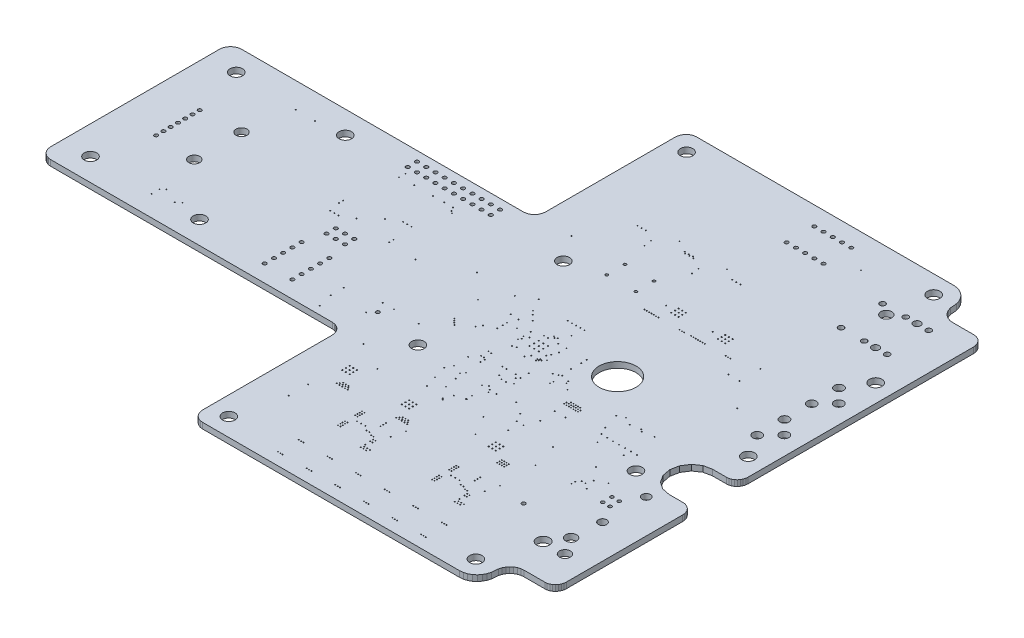
SolidWorks part; units mm, degrees
ref_plane "Front Plane" through (0, 0, 0) normal (0, 0, 1) x (1, 0, 0)
ref_plane "Top Plane" through (0, 0, 0) normal (0, 1, 0) x (1, 0, 0)
ref_plane "Right Plane" through (0, 0, 0) normal (1, 0, 0) x (0, 0, -1)
ref_plane "Dielectric_Layer Layer 1" through (0, 1.6, 0) normal (0, 1, 0) x (1, 0, 0)
sketch "Sketch1" plane through (0, 0, 0) normal (0, 1, 0) x (1, 0, 0)
  line L0 (90.797, -59) -> (91.3624, -58.9424)
  line L1 (91.3624, -58.9424) -> (91.906, -58.7716)
  line L2 (91.906, -58.7716) -> (92.4069, -58.4944)
  line L3 (92.4069, -58.4944) -> (92.8461, -58.1213)
  line L4 (92.8461, -58.1213) -> (93.2064, -57.6667)
  line L5 (93.2064, -57.6667) -> (93.4742, -57.148)
  line L6 (93.4742, -57.148) -> (93.6391, -56.5853)
  line L7 (93.6391, -56.5853) -> (93.6948, -56)
  line L8 (93.6948, -56) -> (93.6948, -24)
  line L9 (93.6948, -24) -> (93.6391, -23.4147)
  line L10 (93.6391, -23.4147) -> (93.4742, -22.8519)
  line L11 (93.4742, -22.8519) -> (93.2064, -22.3333)
  line L12 (93.2064, -22.3333) -> (92.8461, -21.8787)
  line L13 (92.8461, -21.8787) -> (92.4069, -21.5056)
  line L14 (92.4069, -21.5056) -> (91.906, -21.2284)
  line L15 (91.906, -21.2284) -> (91.3624, -21.0576)
  line L16 (91.3624, -21.0576) -> (90.797, -21)
  line L17 (90.797, -21) -> (86.9333, -21)
  line L18 (86.9333, -21) -> (84.7155, -20.5433)
  line L19 (84.7155, -20.5433) -> (82.8353, -19.2426)
  line L20 (82.8353, -19.2426) -> (81.5789, -17.2961)
  line L21 (81.5789, -17.2961) -> (81.1378, -15)
  line L22 (81.1378, -15) -> (81.5789, -12.7039)
  line L23 (81.5789, -12.7039) -> (82.8353, -10.7574)
  line L24 (82.8353, -10.7574) -> (84.7155, -9.4567)
  line L25 (84.7155, -9.4567) -> (86.9333, -9)
  line L26 (86.9333, -9) -> (90.797, -9)
  line L27 (90.797, -9) -> (91.3624, -8.9424)
  line L28 (91.3624, -8.9424) -> (91.906, -8.7716)
  line L29 (91.906, -8.7716) -> (92.4069, -8.4944)
  line L30 (92.4069, -8.4944) -> (92.8461, -8.1213)
  line L31 (92.8461, -8.1213) -> (93.2064, -7.6667)
  line L32 (93.2064, -7.6667) -> (93.4742, -7.148)
  line L33 (93.4742, -7.148) -> (93.6391, -6.5853)
  line L34 (93.6391, -6.5853) -> (93.6948, -6)
  line L35 (93.6948, -6) -> (93.6948, 56)
  line L36 (93.6948, 56) -> (93.6391, 56.5853)
  line L37 (93.6391, 56.5853) -> (93.4742, 57.148)
  line L38 (93.4742, 57.148) -> (93.2064, 57.6667)
  line L39 (93.2064, 57.6667) -> (92.8461, 58.1213)
  line L40 (92.8461, 58.1213) -> (92.4069, 58.4944)
  line L41 (92.4069, 58.4944) -> (91.906, 58.7716)
  line L42 (91.906, 58.7716) -> (91.3624, 58.9424)
  line L43 (91.3624, 58.9424) -> (90.797, 59)
  line L44 (90.797, 59) -> (85.0015, 59)
  line L45 (85.0015, 59) -> (84.2477, 59.0769)
  line L46 (84.2477, 59.0769) -> (83.5229, 59.3045)
  line L47 (83.5229, 59.3045) -> (82.8549, 59.6741)
  line L48 (82.8549, 59.6741) -> (82.2694, 60.1716)
  line L49 (82.2694, 60.1716) -> (81.7889, 60.7777)
  line L50 (81.7889, 60.7777) -> (81.4319, 61.4693)
  line L51 (81.4319, 61.4693) -> (81.212, 62.2196)
  line L52 (81.212, 62.2196) -> (81.1378, 63)
  line L53 (81.1378, 63) -> (81.045, 63.9755)
  line L54 (81.045, 63.9755) -> (80.7701, 64.9134)
  line L55 (80.7701, 64.9134) -> (80.3238, 65.7779)
  line L56 (80.3238, 65.7779) -> (79.7232, 66.5355)
  line L57 (79.7232, 66.5355) -> (78.9913, 67.1573)
  line L58 (78.9913, 67.1573) -> (78.1564, 67.6194)
  line L59 (78.1564, 67.6194) -> (77.2503, 67.9039)
  line L60 (77.2503, 67.9039) -> (76.3081, 68)
  line L61 (76.3081, 68) -> (5.5183, 68)
  line L62 (5.5183, 68) -> (4.953, 67.9424)
  line L63 (4.953, 67.9424) -> (4.4094, 67.7716)
  line L64 (4.4094, 67.7716) -> (3.9084, 67.4944)
  line L65 (3.9084, 67.4944) -> (3.4693, 67.1213)
  line L66 (3.4693, 67.1213) -> (3.1089, 66.6667)
  line L67 (3.1089, 66.6667) -> (2.8411, 66.148)
  line L68 (2.8411, 66.148) -> (2.6762, 65.5853)
  line L69 (2.6762, 65.5853) -> (2.6206, 65)
  line L70 (2.6206, 65) -> (2.6206, 29.337)
  line L71 (2.6206, 29.337) -> (2.5167, 28.5481)
  line L72 (2.5167, 28.5481) -> (2.2122, 27.813)
  line L73 (2.2122, 27.813) -> (1.7278, 27.1817)
  line L74 (1.7278, 27.1817) -> (1.0965, 26.6974)
  line L75 (1.0965, 26.6974) -> (0.3614, 26.3929)
  line L76 (0.3614, 26.3929) -> (-0.4274, 26.289)
  line L77 (-0.4274, 26.289) -> (-77.978, 26.289)
  line L78 (-77.978, 26.289) -> (-78.7669, 26.1851)
  line L79 (-78.7669, 26.1851) -> (-79.502, 25.8806)
  line L80 (-79.502, 25.8806) -> (-80.1333, 25.3963)
  line L81 (-80.1333, 25.3963) -> (-80.6176, 24.765)
  line L82 (-80.6176, 24.765) -> (-80.9221, 24.0299)
  line L83 (-80.9221, 24.0299) -> (-81.026, 23.241)
  line L84 (-81.026, 23.241) -> (-81.026, -23.241)
  line L85 (-81.026, -23.241) -> (-80.9221, -24.0299)
  line L86 (-80.9221, -24.0299) -> (-80.6176, -24.765)
  line L87 (-80.6176, -24.765) -> (-80.1333, -25.3963)
  line L88 (-80.1333, -25.3963) -> (-79.502, -25.8806)
  line L89 (-79.502, -25.8806) -> (-78.7669, -26.1851)
  line L90 (-78.7669, -26.1851) -> (-77.978, -26.289)
  line L91 (-77.978, -26.289) -> (-0.4274, -26.289)
  line L92 (-0.4274, -26.289) -> (0.3614, -26.3929)
  line L93 (0.3614, -26.3929) -> (1.0965, -26.6974)
  line L94 (1.0965, -26.6974) -> (1.7278, -27.1817)
  line L95 (1.7278, -27.1817) -> (2.2122, -27.813)
  line L96 (2.2122, -27.813) -> (2.5167, -28.5481)
  line L97 (2.5167, -28.5481) -> (2.6206, -29.337)
  line L98 (2.6206, -29.337) -> (2.6206, -65)
  line L99 (2.6206, -65) -> (2.6762, -65.5853)
  line L100 (2.6762, -65.5853) -> (2.8411, -66.148)
  line L101 (2.8411, -66.148) -> (3.1089, -66.6667)
  line L102 (3.1089, -66.6667) -> (3.4693, -67.1213)
  line L103 (3.4693, -67.1213) -> (3.9084, -67.4944)
  line L104 (3.9084, -67.4944) -> (4.4094, -67.7716)
  line L105 (4.4094, -67.7716) -> (4.953, -67.9424)
  line L106 (4.953, -67.9424) -> (5.5183, -68)
  line L107 (5.5183, -68) -> (76.3081, -68)
  line L108 (76.3081, -68) -> (77.2503, -67.9039)
  line L109 (77.2503, -67.9039) -> (78.1564, -67.6194)
  line L110 (78.1564, -67.6194) -> (78.9913, -67.1573)
  line L111 (78.9913, -67.1573) -> (79.7232, -66.5355)
  line L112 (79.7232, -66.5355) -> (80.3238, -65.7779)
  line L113 (80.3238, -65.7779) -> (80.7701, -64.9134)
  line L114 (80.7701, -64.9134) -> (81.045, -63.9755)
  line L115 (81.045, -63.9755) -> (81.1378, -63)
  line L116 (81.1378, -63) -> (81.212, -62.2196)
  line L117 (81.212, -62.2196) -> (81.4319, -61.4693)
  line L118 (81.4319, -61.4693) -> (81.7889, -60.7777)
  line L119 (81.7889, -60.7777) -> (82.2694, -60.1716)
  line L120 (82.2694, -60.1716) -> (82.8549, -59.6741)
  line L121 (82.8549, -59.6741) -> (83.5229, -59.3045)
  line L122 (83.5229, -59.3045) -> (84.2477, -59.0769)
  line L123 (84.2477, -59.0769) -> (85.0015, -59)
  line L124 (85.0015, -59) -> (90.797, -59)
extrude "Board_Outline" add sketch "Sketch1" along normal blind 1.6 separate body
sketch "Sketch2" plane through (0, 0, 0) normal (0, 1, 0) x (1, 0, 0)
  circle A0 centre (51.786, 0) radius 5.08
  circle A1 centre (84.391, -36.754) radius 1.15
  circle A2 centre (84.391, -24.714) radius 1.15
  circle A3 centre (80.366, 53.839) radius 1
  circle A4 centre (80.366, 42.409) radius 1
  circle A5 centre (74.016, 51.709) radius 1.5
  circle A6 centre (29.591, -4.191) radius 0.127
  circle A7 centre (29.972, -7.239) radius 0.127
  circle A8 centre (47.244, -22.225) radius 0.127
  circle A9 centre (29.206, -3.306) radius 0.127
  circle A10 centre (29.174, -1.306) radius 0.127
  circle A11 centre (29.19, -4.806) radius 0.127
  circle A12 centre (34.163, -8.001) radius 0.127
  circle A13 centre (38.136, -5.806) radius 0.127
  circle A14 centre (37.993, -2.306) radius 0.127
  circle A15 centre (38.025, -0.306) radius 0.127
  circle A16 centre (34.417, 0.889) radius 0.127
  circle A17 centre (33.909, 0.508) radius 0.127
  circle A18 centre (33.405, 0.893) radius 0.127
  circle A19 centre (55.753, -35.814) radius 0.127
  circle A20 centre (56.388, -35.814) radius 0.127
  circle A21 centre (55.753, -36.449) radius 0.127
  circle A22 centre (56.388, -36.449) radius 0.127
  circle A23 centre (55.753, -37.084) radius 0.127
  circle A24 centre (56.388, -37.084) radius 0.127
  circle A25 centre (57.023, -37.084) radius 0.127
  circle A26 centre (57.023, -36.449) radius 0.127
  circle A27 centre (57.023, -35.814) radius 0.127
  circle A28 centre (57.658, -35.814) radius 0.127
  circle A29 centre (57.658, -36.449) radius 0.127
  circle A30 centre (57.658, -37.084) radius 0.127
  circle A31 centre (50.8, -43.434) radius 0.127
  circle A32 centre (51.435, -43.434) radius 0.127
  circle A33 centre (50.8, -44.069) radius 0.127
  circle A34 centre (51.435, -44.069) radius 0.127
  circle A35 centre (51.435, -44.704) radius 0.127
  circle A36 centre (50.8, -44.704) radius 0.127
  circle A37 centre (50.8, -45.339) radius 0.127
  circle A38 centre (51.435, -45.339) radius 0.127
  circle A39 centre (61.595, -42.164) radius 0.127
  circle A40 centre (35.687, -42.164) radius 0.127
  circle A41 centre (24.892, -43.434) radius 0.127
  circle A42 centre (25.527, -43.434) radius 0.127
  circle A43 centre (24.892, -44.069) radius 0.127
  circle A44 centre (24.892, -44.704) radius 0.127
  circle A45 centre (24.892, -45.339) radius 0.127
  circle A46 centre (25.527, -44.069) radius 0.127
  circle A47 centre (25.527, -44.704) radius 0.127
  circle A48 centre (25.527, -45.339) radius 0.127
  circle A49 centre (14.732, -40.259) radius 0.127
  circle A50 centre (15.113, -39.751) radius 0.127
  circle A51 centre (15.494, -40.259) radius 0.127
  circle A52 centre (15.875, -39.751) radius 0.127
  circle A53 centre (16.256, -40.259) radius 0.127
  circle A54 centre (16.637, -39.751) radius 0.127
  circle A55 centre (17.018, -40.259) radius 0.127
  circle A56 centre (17.399, -39.751) radius 0.127
  circle A57 centre (17.78, -40.259) radius 0.127
  circle A58 centre (17.018, -39.243) radius 0.127
  circle A59 centre (16.256, -39.243) radius 0.127
  circle A60 centre (15.494, -39.243) radius 0.127
  circle A61 centre (31.115, -40.259) radius 0.127
  circle A62 centre (31.496, -39.751) radius 0.127
  circle A63 centre (31.877, -40.259) radius 0.127
  circle A64 centre (32.258, -39.751) radius 0.127
  circle A65 centre (32.639, -40.259) radius 0.127
  circle A66 centre (33.02, -39.751) radius 0.127
  circle A67 centre (33.401, -40.259) radius 0.127
  circle A68 centre (33.782, -39.751) radius 0.127
  circle A69 centre (34.163, -40.259) radius 0.127
  circle A70 centre (33.401, -39.243) radius 0.127
  circle A71 centre (32.639, -39.243) radius 0.127
  circle A72 centre (31.877, -39.243) radius 0.127
  circle A73 centre (50.419, -24.511) radius 0.127
  circle A74 centre (48.514, -24.511) radius 0.127
  circle A75 centre (11.049, -49.784) radius 0.127
  circle A76 centre (61.087, -51.562) radius 0.127
  circle A77 centre (59.182, -50.927) radius 0.127
  circle A78 centre (59.182, -52.197) radius 0.127
  circle A79 centre (59.563, -51.562) radius 0.127
  circle A80 centre (59.944, -52.197) radius 0.127
  circle A81 centre (60.325, -51.562) radius 0.127
  circle A82 centre (60.706, -52.197) radius 0.127
  circle A83 centre (63.627, -58.928) radius 0.127
  circle A84 centre (62.992, -58.928) radius 0.127
  circle A85 centre (62.357, -58.928) radius 0.127
  circle A86 centre (55.753, -58.928) radius 0.127
  circle A87 centre (55.118, -58.928) radius 0.127
  circle A88 centre (54.483, -58.928) radius 0.127
  circle A89 centre (47.879, -58.928) radius 0.127
  circle A90 centre (47.244, -58.928) radius 0.127
  circle A91 centre (46.609, -58.928) radius 0.127
  circle A92 centre (40.005, -58.928) radius 0.127
  circle A93 centre (39.37, -58.928) radius 0.127
  circle A94 centre (38.735, -58.928) radius 0.127
  circle A95 centre (32.131, -58.928) radius 0.127
  circle A96 centre (31.496, -58.928) radius 0.127
  circle A97 centre (30.861, -58.928) radius 0.127
  circle A98 centre (24.257, -58.928) radius 0.127
  circle A99 centre (23.622, -58.928) radius 0.127
  circle A100 centre (22.987, -58.928) radius 0.127
  circle A101 centre (41.529, 23.622) radius 0.127
  circle A102 centre (39.497, 19.685) radius 0.127
  circle A103 centre (40.132, 19.685) radius 0.127
  circle A104 centre (40.767, 19.685) radius 0.127
  circle A105 centre (41.402, 19.685) radius 0.127
  circle A106 centre (42.037, 19.685) radius 0.127
  circle A107 centre (42.672, 19.685) radius 0.127
  circle A108 centre (43.307, 19.685) radius 0.127
  circle A109 centre (52.197, 19.812) radius 0.127
  circle A110 centre (52.832, 19.812) radius 0.127
  circle A111 centre (53.467, 19.812) radius 0.127
  circle A112 centre (54.102, 19.812) radius 0.127
  circle A113 centre (54.737, 19.812) radius 0.127
  circle A114 centre (55.372, 19.812) radius 0.127
  circle A115 centre (56.007, 19.812) radius 0.127
  circle A116 centre (35.179, -51.562) radius 0.127
  circle A117 centre (33.274, -50.927) radius 0.127
  circle A118 centre (33.274, -52.197) radius 0.127
  circle A119 centre (33.655, -51.562) radius 0.127
  circle A120 centre (34.036, -52.197) radius 0.127
  circle A121 centre (34.417, -51.562) radius 0.127
  circle A122 centre (34.798, -52.197) radius 0.127
  circle A123 centre (-50.8, 19.304) radius 0.127
  circle A124 centre (54.229, 23.749) radius 0.127
  circle A125 centre (57.658, -47.879) radius 0.127
  circle A126 centre (58.293, -47.879) radius 0.127
  circle A127 centre (56.769, -47.371) radius 0.127
  circle A128 centre (56.007, -47.371) radius 0.127
  circle A129 centre (54.737, -46.482) radius 0.127
  circle A130 centre (53.594, -46.482) radius 0.127
  circle A131 centre (52.451, -46.482) radius 0.127
  circle A132 centre (56.896, -44.45) radius 0.127
  circle A133 centre (56.896, -42.926) radius 0.127
  circle A134 centre (56.896, -43.688) radius 0.127
  circle A135 centre (30.988, -42.926) radius 0.127
  circle A136 centre (30.988, -43.688) radius 0.127
  circle A137 centre (30.988, -44.45) radius 0.127
  circle A138 centre (27.686, -46.482) radius 0.127
  circle A139 centre (26.543, -46.482) radius 0.127
  circle A140 centre (28.829, -46.482) radius 0.127
  circle A141 centre (30.099, -47.371) radius 0.127
  circle A142 centre (30.861, -47.371) radius 0.127
  circle A143 centre (31.877, -47.879) radius 0.127
  circle A144 centre (32.512, -47.879) radius 0.127
  circle A145 centre (37.465, 34.798) radius 0.127
  circle A146 centre (31.75, 38.608) radius 0.127
  circle A147 centre (32.893, 38.608) radius 0.127
  circle A148 centre (34.036, 38.608) radius 0.127
  circle A149 centre (44.45, 38.862) radius 0.127
  circle A150 centre (45.593, 38.862) radius 0.127
  circle A151 centre (46.736, 38.862) radius 0.127
  circle A152 centre (24.257, 34.925) radius 0.127
  circle A153 centre (20.828, 38.735) radius 0.127
  circle A154 centre (19.685, 38.735) radius 0.127
  circle A155 centre (18.542, 38.735) radius 0.127
  circle A156 centre (-14.605, 7.366) radius 0.127
  circle A157 centre (-13.462, 7.366) radius 0.127
  circle A158 centre (-12.319, 7.366) radius 0.127
  circle A159 centre (-27.305, 0) radius 0.127
  circle A160 centre (-26.162, 0) radius 0.127
  circle A161 centre (-25.019, 0) radius 0.127
  circle A162 centre (-27.94, 4.191) radius 0.127
  circle A163 centre (-27.94, 3.048) radius 0.127
  circle A164 centre (-11.684, 1.778) radius 0.127
  circle A165 centre (-11.684, 0.635) radius 0.127
  circle A166 centre (-7.112, -20.066) radius 0.127
  circle A167 centre (-7.112, -16.51) radius 0.127
  circle A168 centre (3.429, -17.653) radius 0.508
  circle A169 centre (33.528, 38.989) radius 0.127
  circle A170 centre (32.385, 38.989) radius 0.127
  circle A171 centre (31.242, 38.989) radius 0.127
  circle A172 centre (74.295, -30.988) radius 0.127
  circle A173 centre (43.561, -4.572) radius 0.127
  circle A174 centre (73.279, -28.067) radius 0.127
  circle A175 centre (52.832, -12.573) radius 0.127
  circle A176 centre (52.197, -12.573) radius 0.127
  circle A177 centre (53.467, -12.573) radius 0.127
  circle A178 centre (54.102, -12.573) radius 0.127
  circle A179 centre (51.562, -12.573) radius 0.127
  circle A180 centre (51.562, -13.208) radius 0.127
  circle A181 centre (52.197, -13.208) radius 0.127
  circle A182 centre (52.832, -13.208) radius 0.127
  circle A183 centre (53.467, -13.208) radius 0.127
  circle A184 centre (54.102, -13.208) radius 0.127
  circle A185 centre (54.737, -13.208) radius 0.127
  circle A186 centre (50.927, -13.208) radius 0.127
  circle A187 centre (50.927, -13.843) radius 0.127
  circle A188 centre (51.562, -13.843) radius 0.127
  circle A189 centre (52.197, -13.843) radius 0.127
  circle A190 centre (52.832, -13.843) radius 0.127
  circle A191 centre (53.467, -13.843) radius 0.127
  circle A192 centre (54.102, -13.843) radius 0.127
  circle A193 centre (54.737, -13.843) radius 0.127
  circle A194 centre (49.53, -27.813) radius 0.127
  circle A195 centre (31.623, 6.477) radius 0.127
  circle A196 centre (32.766, 6.477) radius 0.127
  circle A197 centre (33.909, 6.477) radius 0.127
  circle A198 centre (35.052, 6.477) radius 0.127
  circle A199 centre (36.195, 6.477) radius 0.127
  circle A200 centre (24.539, -0.028) radius 0.127
  circle A201 centre (23.749, -2.413) radius 0.127
  circle A202 centre (23.749, -3.556) radius 0.127
  circle A203 centre (23.749, -5.08) radius 0.127
  circle A204 centre (26.396, -2.306) radius 0.127
  circle A205 centre (28.829, -11.811) radius 0.127
  circle A206 centre (33.528, -13.462) radius 0.127
  circle A207 centre (34.671, -13.462) radius 0.127
  circle A208 centre (-54.925, -17.465) radius 0.127
  circle A209 centre (-50.734, -19.365) radius 0.127
  circle A210 centre (24.483, 4.036) radius 0.127
  circle A211 centre (69.088, -43.18) radius 0.508
  circle A212 centre (22.987, -64.643) radius 0.127
  circle A213 centre (23.622, -64.643) radius 0.127
  circle A214 centre (24.257, -64.643) radius 0.127
  circle A215 centre (30.861, -64.643) radius 0.127
  circle A216 centre (31.496, -64.643) radius 0.127
  circle A217 centre (32.131, -64.643) radius 0.127
  circle A218 centre (38.735, -64.643) radius 0.127
  circle A219 centre (39.37, -64.643) radius 0.127
  circle A220 centre (40.005, -64.643) radius 0.127
  circle A221 centre (46.609, -64.643) radius 0.127
  circle A222 centre (47.244, -64.643) radius 0.127
  circle A223 centre (47.879, -64.643) radius 0.127
  circle A224 centre (54.483, -64.643) radius 0.127
  circle A225 centre (55.118, -64.643) radius 0.127
  circle A226 centre (55.753, -64.643) radius 0.127
  circle A227 centre (62.357, -64.643) radius 0.127
  circle A228 centre (62.992, -64.643) radius 0.127
  circle A229 centre (63.627, -64.643) radius 0.127
  circle A230 centre (64.897, -16.002) radius 0.127
  circle A231 centre (66.548, -16.002) radius 0.127
  circle A232 centre (68.199, -16.002) radius 0.127
  circle A233 centre (69.85, -16.002) radius 0.127
  circle A234 centre (71.501, -16.002) radius 0.127
  circle A235 centre (73.152, -16.002) radius 0.127
  circle A236 centre (63.246, -15.875) radius 0.127
  circle A237 centre (29.972, -22.733) radius 0.127
  circle A238 centre (25.781, -21.717) radius 0.127
  circle A239 centre (29.972, -19.939) radius 0.127
  circle A240 centre (37.211, -13.462) radius 0.127
  circle A241 centre (36.449, -16.637) radius 0.127
  circle A242 centre (37.719, -16.637) radius 0.127
  circle A243 centre (39.243, -16.002) radius 0.127
  circle A244 centre (35.179, -16.002) radius 0.127
  circle A245 centre (35.179, -20.701) radius 0.127
  circle A246 centre (37.338, -20.701) radius 0.127
  circle A247 centre (37.719, -21.463) radius 0.127
  circle A248 centre (39.243, -20.828) radius 0.127
  circle A249 centre (21.082, -6.35) radius 0.127
  circle A250 centre (20.32, -7.62) radius 0.127
  circle A251 centre (22.225, 0.127) radius 0.127
  circle A252 centre (43.307, -7.747) radius 0.127
  circle A253 centre (43.942, -7.366) radius 0.127
  circle A254 centre (43.561, -0.254) radius 0.127
  circle A255 centre (43.561, -1.778) radius 0.127
  circle A256 centre (-56.134, 19.304) radius 0.127
  circle A257 centre (11.049, -44.45) radius 0.127
  circle A258 centre (42.926, -28.067) radius 0.127
  circle A259 centre (9.017, -27.178) radius 0.127
  circle A260 centre (26.797, -25.273) radius 0.127
  circle A261 centre (66.548, 15.748) radius 0.127
  circle A262 centre (69.596, 15.748) radius 0.127
  circle A263 centre (61.595, -32.385) radius 0.127
  circle A264 centre (14.224, -0.889) radius 0.127
  circle A265 centre (18.415, 5.08) radius 0.127
  circle A266 centre (75.819, 8.89) radius 0.127
  circle A267 centre (59.944, 58.801) radius 0.127
  circle A268 centre (42.164, -8.255) radius 0.127
  circle A269 centre (11.811, -14.732) radius 0.127
  circle A270 centre (46.355, -8.636) radius 0.127
  circle A271 centre (60.96, -9.525) radius 0.127
  circle A272 centre (1.905, -19.304) radius 0.127
  circle A273 centre (16.891, -31.242) radius 0.127
  circle A274 centre (71.247, -9.271) radius 0.127
  circle A275 centre (67.564, -9.271) radius 0.127
  circle A276 centre (70.358, -24.511) radius 0.127
  circle A277 centre (51.689, -21.209) radius 0.127
  circle A278 centre (30.341, -2.806) radius 0.127
  circle A279 centre (30.905, -6.858) radius 0.127
  circle A280 centre (34.889, -6.858) radius 0.127
  circle A281 centre (36.937, -4.806) radius 0.127
  circle A282 centre (35.762, -0.329) radius 0.127
  circle A283 centre (31.905, -0.353) radius 0.127
  circle A284 centre (54.328, -16.919) radius 0.127
  circle A285 centre (43.942, -20.066) radius 0.127
  circle A286 centre (51.336, -16.863) radius 0.127
  circle A287 centre (37.084, -6.985) radius 0.127
  circle A288 centre (36.576, -6.858) radius 0.127
  circle A289 centre (36.957, -6.477) radius 0.127
  circle A290 centre (37.465, -6.604) radius 0.127
  circle A291 centre (36.703, -7.366) radius 0.127
  circle A292 centre (26.67, -19.939) radius 0.127
  circle A293 centre (33.782, -27.051) radius 0.127
  circle A294 centre (36.322, -19.939) radius 0.127
  circle A295 centre (36.322, -26.162) radius 0.1905
  circle A296 centre (36.322, -24.638) radius 0.127
  circle A297 centre (71.374, -17.907) radius 0.127
  circle A298 centre (32.893, -29.21) radius 0.127
  circle A299 centre (33.274, -29.591) radius 0.127
  circle A300 centre (30.607, -26.035) radius 0.127
  circle A301 centre (1.905, -14.732) radius 0.127
  circle A302 centre (4.953, -14.732) radius 0.127
  circle A303 centre (59.69, -25.654) radius 0.127
  circle A304 centre (44.069, -10.922) radius 0.127
  circle A305 centre (38.1, -14.351) radius 0.127
  circle A306 centre (44.196, -10.033) radius 0.127
  circle A307 centre (38.735, -13.716) radius 0.127
  circle A308 centre (33.02, -0.381) radius 0.127
  circle A309 centre (27.94, -11.684) radius 0.127
  circle A310 centre (26.543, -15.875) radius 0.127
  circle A311 centre (29.276, -20.889) radius 0.127
  circle A312 centre (26.797, 1.651) radius 0.127
  circle A313 centre (25.4, 3.048) radius 0.127
  circle A314 centre (35.687, 3.429) radius 0.127
  circle A315 centre (7.62, 5.461) radius 0.127
  circle A316 centre (-3.937, 0.127) radius 0.127
  circle A317 centre (-49.53, -18.415) radius 0.127
  circle A318 centre (46.101, -7.874) radius 0.127
  circle A319 centre (48.006, -10.033) radius 0.127
  circle A320 centre (-6.096, -24.13) radius 0.127
  circle A321 centre (-55.88, -20.574) radius 0.127
  circle A322 centre (-55.88, -18.415) radius 0.127
  circle A323 centre (62.738, -8.636) radius 0.127
  circle A324 centre (28.829, -13.843) radius 0.127
  circle A325 centre (-13.589, 17.653) radius 0.127
  circle A326 centre (28.067, -13.843) radius 0.127
  circle A327 centre (29.464, -14.224) radius 0.127
  circle A328 centre (-16.637, 17.653) radius 0.127
  circle A329 centre (29.464, -15.367) radius 0.127
  circle A330 centre (-21.844, 17.653) radius 0.127
  circle A331 centre (68.199, -9.779) radius 0.127
  circle A332 centre (62.23, -13.843) radius 0.127
  circle A333 centre (15.494, -8.636) radius 0.127
  circle A334 centre (-9.906, 16.129) radius 0.127
  circle A335 centre (-25.781, 17.399) radius 0.127
  circle A336 centre (16.002, -9.144) radius 0.127
  circle A337 centre (-10.541, 16.637) radius 0.127
  circle A338 centre (-25.781, 19.177) radius 0.127
  circle A339 centre (16.51, -9.652) radius 0.127
  circle A340 centre (-11.176, 17.653) radius 0.127
  circle A341 centre (17.018, -10.16) radius 0.127
  circle A342 centre (33.147, -48.641) radius 0.127
  circle A343 centre (33.147, -49.403) radius 0.127
  circle A344 centre (33.782, -49.403) radius 0.127
  circle A345 centre (33.782, -48.641) radius 0.127
  circle A346 centre (34.925, -45.593) radius 0.127
  circle A347 centre (24.892, -48.133) radius 0.127
  circle A348 centre (25.527, -48.133) radius 0.127
  circle A349 centre (25.527, -48.768) radius 0.127
  circle A350 centre (25.527, -49.403) radius 0.127
  circle A351 centre (25.527, -50.038) radius 0.127
  circle A352 centre (24.892, -50.038) radius 0.127
  circle A353 centre (24.892, -49.403) radius 0.127
  circle A354 centre (24.892, -48.768) radius 0.127
  circle A355 centre (59.055, -48.641) radius 0.127
  circle A356 centre (59.69, -48.641) radius 0.127
  circle A357 centre (59.055, -49.403) radius 0.127
  circle A358 centre (59.69, -49.403) radius 0.127
  circle A359 centre (60.833, -45.593) radius 0.127
  circle A360 centre (50.8, -50.038) radius 0.127
  circle A361 centre (51.435, -50.038) radius 0.127
  circle A362 centre (50.8, -49.403) radius 0.127
  circle A363 centre (51.435, -49.403) radius 0.127
  circle A364 centre (51.435, -48.768) radius 0.127
  circle A365 centre (50.8, -48.768) radius 0.127
  circle A366 centre (50.8, -48.133) radius 0.127
  circle A367 centre (51.435, -48.133) radius 0.127
  circle A368 centre (11.938, 27.178) radius 0.127
  circle A369 centre (-73.223, 20.066) radius 1.7145
  circle A370 centre (-43.223, 20.066) radius 1.7145
  circle A371 centre (-73.223, -20.066) radius 1.7145
  circle A372 centre (-43.223, -20.066) radius 1.7145
  circle A373 centre (16.773, 20.066) radius 1.7145
  circle A374 centre (16.773, -19.939) radius 1.7145
  circle A375 centre (7.773, -62.992) radius 1.7145
  circle A376 centre (75.773, -62.992) radius 1.7145
  circle A377 centre (76.773, -19.939) radius 1.7145
  circle A378 centre (7.773, 62.992) radius 1.7145
  circle A379 centre (75.773, 62.992) radius 1.7145
  circle A380 centre (88.773, 34.036) radius 1.7145
  circle A381 centre (88.773, -1.016) radius 1.7145
  circle A382 centre (22.479, 7.62) radius 0.127
  circle A383 centre (45.974, -33.274) radius 0.127
  circle A384 centre (27.813, -28.448) radius 0.127
  circle A385 centre (64.643, -18.415) radius 0.127
  circle A386 centre (38.735, -11.43) radius 0.127
  circle A387 centre (71.755, -29.845) radius 0.127
  circle A388 centre (70.993, -30.861) radius 0.127
  circle A389 centre (72.771, -29.845) radius 0.127
  circle A390 centre (70.993, -31.877) radius 0.127
  circle A391 centre (64.897, -9.779) radius 0.127
  circle A392 centre (37.465, -3.937) radius 0.127
  circle A393 centre (75.946, -26.67) radius 0.127
  circle A394 centre (49.149, 19.685) radius 0.127
  circle A395 centre (50.419, 19.685) radius 0.127
  circle A396 centre (37.211, 36.83) radius 0.127
  circle A397 centre (24.003, 36.957) radius 0.127
  circle A398 centre (-17.78, 5.588) radius 0.127
  circle A399 centre (49.784, 19.685) radius 0.127
  circle A400 centre (69.596, 21.463) radius 0.127
  circle A401 centre (61.722, 19.812) radius 0.127
  circle A402 centre (62.992, 19.812) radius 0.127
  circle A403 centre (41.275, 40.64) radius 0.127
  circle A404 centre (-21.844, 1.778) radius 0.127
  circle A405 centre (62.357, 19.812) radius 0.127
  circle A406 centre (28.067, 40.767) radius 0.127
extrude "NPTH" cut sketch "Sketch2" along normal through all
sketch "Sketch3" plane through (0, 0, 0) normal (0, 1, 0) x (1, 0, 0)
  circle A0 centre (26.04, 22.77) radius 0.375
  circle A1 centre (26.04, 27.77) radius 0.375
  circle A2 centre (34.04, 22.77) radius 0.375
  circle A3 centre (34.04, 27.77) radius 0.375
  circle A4 centre (80.82, -49.53) radius 1.75
  circle A5 centre (86.82, -49.53) radius 1.5
  circle A6 centre (83.82, -44.83) radius 1.5
  circle A7 centre (79.68, -29.48) radius 0.46
  circle A8 centre (79.68, -31.98) radius 0.46
  circle A9 centre (81.68, -31.98) radius 0.46
  circle A10 centre (81.68, -29.48) radius 0.46
  circle A11 centre (77.22, 53.84) radius 0.75
  circle A12 centre (77.22, 42.41) radius 0.75
  circle A13 centre (83.57, 53.84) radius 0.75
  circle A14 centre (83.57, 42.41) radius 0.75
  circle A15 centre (70.87, 53.84) radius 0.75
  circle A16 centre (70.87, 42.41) radius 0.75
  circle A17 centre (84.95, 27.76) radius 1.25
  circle A18 centre (88.65, 24.01) radius 1.25
  circle A19 centre (84.95, 20.26) radius 1.25
  circle A20 centre (84.95, 12.76) radius 1.25
  circle A21 centre (88.65, 9.01) radius 1.25
  circle A22 centre (84.95, 5.26) radius 1.25
  circle A23 centre (-22.35, -5.97) radius 0.51
  circle A24 centre (-22.35, -3.43) radius 0.51
  circle A25 centre (-19.81, -5.97) radius 0.51
  circle A26 centre (-19.81, -3.43) radius 0.51
  circle A27 centre (-17.27, -5.97) radius 0.51
  circle A28 centre (-17.27, -3.43) radius 0.51
  circle A29 centre (-27.05, 21.08) radius 0.51
  circle A30 centre (-27.05, 23.62) radius 0.51
  circle A31 centre (-24.51, 21.08) radius 0.51
  circle A32 centre (-24.51, 23.62) radius 0.51
  circle A33 centre (-21.97, 21.08) radius 0.51
  circle A34 centre (-21.97, 23.62) radius 0.51
  circle A35 centre (-19.43, 21.08) radius 0.51
  circle A36 centre (-19.43, 23.62) radius 0.51
  circle A37 centre (-16.89, 21.08) radius 0.51
  circle A38 centre (-16.89, 23.62) radius 0.51
  circle A39 centre (-14.35, 21.08) radius 0.51
  circle A40 centre (-14.35, 23.62) radius 0.51
  circle A41 centre (-11.81, 21.08) radius 0.51
  circle A42 centre (-11.81, 23.62) radius 0.51
  circle A43 centre (-9.27, 21.08) radius 0.51
  circle A44 centre (-9.27, 23.62) radius 0.51
  circle A45 centre (-6.73, 21.08) radius 0.51
  circle A46 centre (-6.73, 23.62) radius 0.51
  circle A47 centre (-4.19, 21.08) radius 0.51
  circle A48 centre (-4.19, 23.62) radius 0.51
  circle A49 centre (-16.13, -21.59) radius 0.5
  circle A50 centre (-16.13, -19.05) radius 0.5
  circle A51 centre (-16.13, -16.51) radius 0.5
  circle A52 centre (-16.13, -13.97) radius 0.5
  circle A53 centre (-16.13, -11.43) radius 0.5
  circle A54 centre (-23.75, -11.43) radius 0.5
  circle A55 centre (-23.75, -13.97) radius 0.5
  circle A56 centre (-23.75, -16.51) radius 0.5
  circle A57 centre (-23.75, -19.05) radius 0.5
  circle A58 centre (-23.75, -21.59) radius 0.5
  circle A59 centre (53.21, 62.87) radius 0.5
  circle A60 centre (50.67, 62.87) radius 0.5
  circle A61 centre (48.13, 62.87) radius 0.5
  circle A62 centre (45.59, 62.87) radius 0.5
  circle A63 centre (43.05, 62.87) radius 0.5
  circle A64 centre (43.05, 55.25) radius 0.5
  circle A65 centre (45.59, 55.25) radius 0.5
  circle A66 centre (48.13, 55.25) radius 0.5
  circle A67 centre (50.67, 55.25) radius 0.5
  circle A68 centre (53.21, 55.25) radius 0.5
  circle A69 centre (32.38, -2.29) radius 0.15
  circle A70 centre (33.66, -2.29) radius 0.15
  circle A71 centre (34.93, -2.29) radius 0.15
  circle A72 centre (32.38, -3.56) radius 0.15
  circle A73 centre (33.66, -3.56) radius 0.15
  circle A74 centre (34.93, -3.56) radius 0.15
  circle A75 centre (32.38, -4.83) radius 0.15
  circle A76 centre (33.66, -4.83) radius 0.15
  circle A77 centre (34.93, -4.83) radius 0.15
  circle A78 centre (29.72, -35.31) radius 0.15
  circle A79 centre (30.72, -35.31) radius 0.15
  circle A80 centre (28.72, -35.31) radius 0.15
  circle A81 centre (28.72, -36.31) radius 0.15
  circle A82 centre (29.72, -36.31) radius 0.15
  circle A83 centre (30.72, -36.31) radius 0.15
  circle A84 centre (30.72, -34.31) radius 0.15
  circle A85 centre (29.72, -34.31) radius 0.15
  circle A86 centre (28.72, -34.31) radius 0.15
  circle A87 centre (51.69, -33.4) radius 0.15
  circle A88 centre (51.69, -34.4) radius 0.15
  circle A89 centre (51.69, -32.4) radius 0.15
  circle A90 centre (50.69, -32.4) radius 0.15
  circle A91 centre (50.69, -33.4) radius 0.15
  circle A92 centre (50.69, -34.4) radius 0.15
  circle A93 centre (52.69, -34.4) radius 0.15
  circle A94 centre (52.69, -33.4) radius 0.15
  circle A95 centre (52.69, -32.4) radius 0.15
  circle A96 centre (13.34, -35.31) radius 0.15
  circle A97 centre (14.34, -35.31) radius 0.15
  circle A98 centre (12.34, -35.31) radius 0.15
  circle A99 centre (12.34, -36.31) radius 0.15
  circle A100 centre (13.34, -36.31) radius 0.15
  circle A101 centre (14.34, -36.31) radius 0.15
  circle A102 centre (14.34, -34.31) radius 0.15
  circle A103 centre (13.34, -34.31) radius 0.15
  circle A104 centre (12.34, -34.31) radius 0.15
  circle A105 centre (44.96, 23.62) radius 0.15
  circle A106 centre (44.96, 22.62) radius 0.15
  circle A107 centre (44.96, 24.62) radius 0.15
  circle A108 centre (43.96, 24.62) radius 0.15
  circle A109 centre (43.96, 23.62) radius 0.15
  circle A110 centre (43.96, 22.62) radius 0.15
  circle A111 centre (45.96, 22.62) radius 0.15
  circle A112 centre (45.96, 23.62) radius 0.15
  circle A113 centre (45.96, 24.62) radius 0.15
  circle A114 centre (57.66, 23.75) radius 0.15
  circle A115 centre (57.66, 22.75) radius 0.15
  circle A116 centre (57.66, 24.75) radius 0.15
  circle A117 centre (56.66, 24.75) radius 0.15
  circle A118 centre (56.66, 23.75) radius 0.15
  circle A119 centre (56.66, 22.75) radius 0.15
  circle A120 centre (58.66, 22.75) radius 0.15
  circle A121 centre (58.66, 23.75) radius 0.15
  circle A122 centre (58.66, 24.75) radius 0.15
  circle A123 centre (-69.22, 6) radius 0.5
  circle A124 centre (-69.22, -6) radius 0.5
  circle A125 centre (-69.22, 0) radius 0.5
  circle A126 centre (-69.22, 4) radius 0.5
  circle A127 centre (-58.22, -6.5) radius 1.5
  circle A128 centre (-58.22, 6.5) radius 1.5
  circle A129 centre (-69.22, -4) radius 0.5
  circle A130 centre (-69.22, -2) radius 0.5
  circle A131 centre (-69.22, 2) radius 0.5
extrude "PTH" cut sketch "Sketch3" along normal through all
